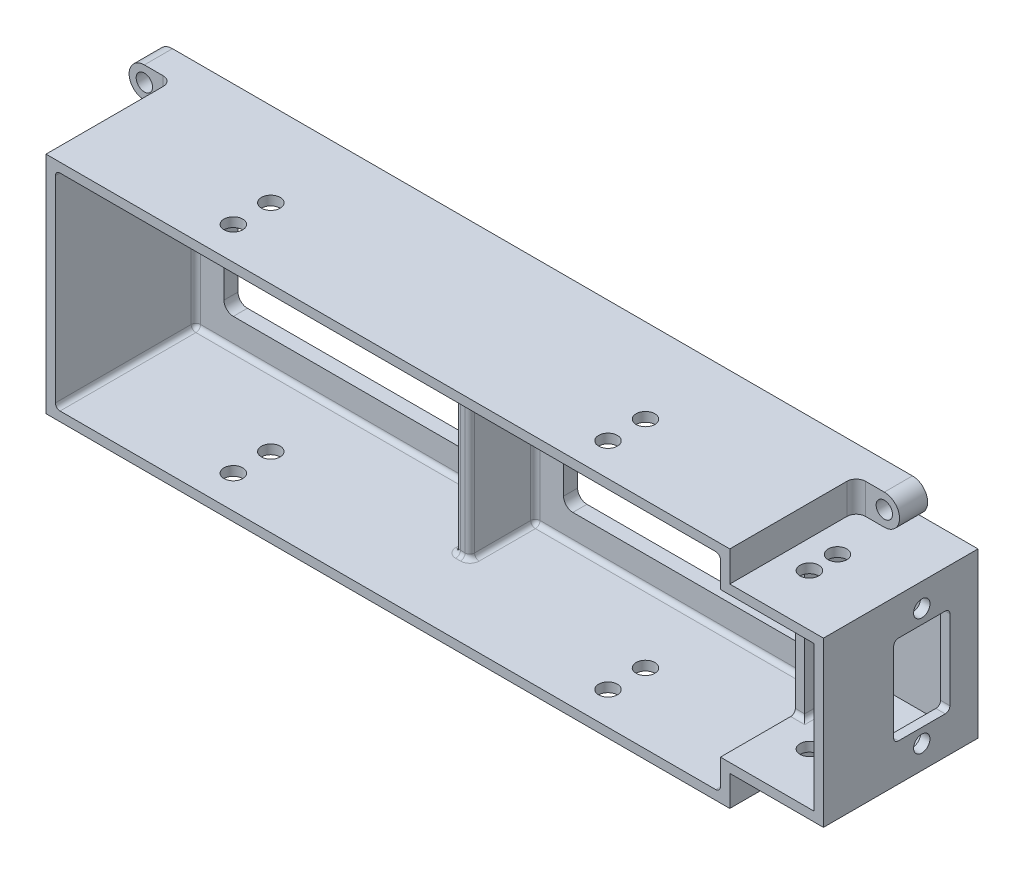
SolidWorks part; units mm, degrees
ref_plane "Top Plane" through (0, 0, 0) normal (0, 0, 1) x (1, 0, 0)
ref_plane "Right Plane" through (0, 0, 0) normal (0, 1, 0) x (1, 0, 0)
ref_plane "Front Plane" through (0, 0, 0) normal (1, 0, 0) x (0, 0, -1)
sketch "Sketch1" plane through (0, 0, 0) normal (0, 0, 1) x (1, 0, 0)
  line L0 (-70, 21) -> (70, -21) construction
  line L1 (-70, 21) -> (70, 21) construction
  line L2 (-70, 21) -> (-70, -21) construction
  line L3 (-70, -21) -> (70, -21) construction
  line L4 (70, 21) -> (70, -21) construction
  line L5 (-71, 22) -> (71, 22) construction
  line L6 (71, 22) -> (71, -22) construction
  line L7 (-71, -22) -> (71, -22) construction
  line L8 (-71, 22) -> (-71, -22) construction
  line L9 (-73, 24) -> (73, 24)
  line L10 (73, 24) -> (73, 17.5)
  line L11 (-73, -24) -> (73, -24)
  line L12 (-73, 24) -> (-73, -24)
  line L13 (73, 17.5) -> (93, 17.5)
  line L14 (93, 17.5) -> (93, -17.5)
  line L15 (-78.4215, 0) -> (137.9248, 0) construction
  line L16 (73, -17.5) -> (93, -17.5)
  line L17 (73, -17.5) -> (73, -24)
  line L18 (73, 24) -> (73, -24) construction
  point P18 (0, 0)
  point P20 (93, 0)
  dimension "D1" = 140
  dimension "D2" = 42
  dimension "D5" = 35
  dimension "D6" = 20
  dimension "D3" = 1
  dimension "D4" = 2
extrude "Boss-Extrude1" add sketch "Sketch1" along normal mid plane 3
sketch "Sketch2" plane through (0, 0, 1.5) normal (0, 0, 1) x (1, 0, 0)
  line L0 (-71, 22) -> (71, 22) construction
  line L1 (71, 22) -> (71, -22) construction
  line L2 (-71, -22) -> (71, -22) construction
  line L3 (-71, 22) -> (-71, -22) construction
  line L4 (-71, 22) -> (71, 22)
  line L5 (71, 22) -> (71, 15.5)
  line L6 (-71, -22) -> (71, -22)
  line L7 (-71, 22) -> (-71, -22)
  line L8 (71, -15.5) -> (91, -15.5)
  line L9 (91, -15.5) -> (91, 15.5)
  line L10 (91, 15.5) -> (71, 15.5)
  line L11 (91, 15.5) -> (73, 15.5) construction
  line L12 (-73, 24) -> (-73, -24)
  line L13 (-73, -24) -> (73, -24)
  line L14 (73, 17.5) -> (73, 24)
  line L15 (73, 24) -> (-73, 24)
  line L16 (-73, 24) -> (-73, -24)
  line L17 (-73, -24) -> (73, -24)
  line L18 (73, 17.5) -> (73, 24)
  line L19 (73, 24) -> (-73, 24)
  line L20 (73, -15.5) -> (91, -15.5) construction
  line L21 (71, -15.5) -> (71, -22)
  line L24 (73, -24) -> (73, -17.5)
  line L25 (73, -24) -> (73, -17.5)
  line L26 (73, -17.5) -> (93, -17.5)
  line L27 (73, -17.5) -> (93, -17.5)
  line L28 (93, -17.5) -> (93, 17.5)
  line L29 (93, -17.5) -> (93, 17.5)
  line L30 (93, 17.5) -> (73, 17.5)
  line L31 (93, 17.5) -> (73, 17.5)
  point P11 (71, 15.5)
  point P14 (71, -15.5)
  point P18 (71, 15.5)
  dimension "D1" = 0
  dimension "D2" = 2
extrude "Boss-Extrude2" add sketch "Sketch2" along normal blind 30
sketch "Sketch3" plane through (0, 0, 1.5) normal (0, 0, 1) x (1, 0, 0)
  line L0 (91, 15.5) -> (71, 15.5) construction
  line L1 (-1.5, 22) -> (1.5, 22)
  line L2 (-1.5, 22) -> (-1.5, -22)
  line L3 (-1.5, -22) -> (1.5, -22)
  line L4 (1.5, 22) -> (1.5, -22)
  line L5 (71, -15.5) -> (73, -15.5)
  line L6 (-1.5, 22) -> (1.5, -22) construction
  line L7 (71, -15.5) -> (71, 15.5)
  line L8 (71, 15.5) -> (73, 15.5)
  line L9 (-71, -22) -> (71, -22) construction
  line L10 (73, -15.5) -> (73, 15.5)
  dimension "D1" = 3
  dimension "D2" = 2
extrude "Boss-Extrude3" add sketch "Sketch3" along normal blind 14
sketch "Sketch5" plane through (0, 0, 1.5) normal (0, 0, 1) x (1, 0, 0)
  line L4 (0, -30.015) -> (0, 35.8775) construction
  line L5 (65, 16) -> (65, -16)
  line L6 (7.5, 16) -> (65, 16)
  line L7 (7.5, -16) -> (7.5, 16)
  line L8 (-65, -16) -> (-7.5, -16)
  line L9 (-7.5, -16) -> (-7.5, 16)
  line L10 (-7.5, 16) -> (-65, 16)
  line L11 (-65, 16) -> (-65, -16)
  line L12 (-65, -16) -> (-7.5, -16)
  line L13 (-7.5, -16) -> (-7.5, 16)
  line L14 (-7.5, 16) -> (-65, 16)
  line L15 (-65, 16) -> (-65, -16)
  line L16 (65, -16) -> (7.5, -16)
  dimension "D1" = 6
extrude "Cut-Extrude1" cut sketch "Sketch5" against normal through all
sketch "Sketch6" plane through (0, 0, -1.5) normal (0, 0, -1) x (-1, 0, 0)
  line L0 (-79, 24) -> (-73, 24)
  line L1 (-93, 17.5) -> (-73, 17.5) construction
  line L2 (-73, 17.5) -> (-73, 24) construction
  line L3 (-79, 17.5) -> (-73, 17.5)
  line L4 (-73, 17.5) -> (-73, 24)
  line L5 (-108.1843, 0) -> (78.2725, 0) construction
  line L6 (-73, -17.5) -> (-73, -24)
  line L7 (-79, -17.5) -> (-73, -17.5)
  line L8 (-79, -24) -> (-73, -24)
  line L9 (0, 28.6257) -> (0, -28.9986) construction
  line L10 (79, -24) -> (73, -24)
  line L11 (79, -17.5) -> (73, -17.5)
  line L12 (73, -17.5) -> (73, -24)
  line L13 (73, 17.5) -> (73, 24)
  line L14 (79, 17.5) -> (73, 17.5)
  line L15 (79, 24) -> (73, 24)
  arc A0 (-79, 24) -> (-79, 17.5) centre (-79, 20.75) ccw
  arc A1 (-79, -24) -> (-79, -17.5) centre (-79, -20.75) cw
  arc A2 (79, -24) -> (79, -17.5) centre (79, -20.75) ccw
  arc A3 (79, 24) -> (79, 17.5) centre (79, 20.75) cw
  circle A4 centre (-79, 20.75) radius 3 construction
  circle A5 centre (-79, 20.75) radius 1.75 construction
  circle A6 centre (-79, -20.75) radius 1.75 construction
  circle A7 centre (-79, -20.75) radius 3 construction
  circle A8 centre (79, -20.75) radius 3 construction
  circle A9 centre (79, -20.75) radius 1.75 construction
  circle A10 centre (79, 20.75) radius 1.75 construction
  circle A11 centre (79, 20.75) radius 3 construction
  dimension "D1" = 6.5
  dimension "D3" = 6
  dimension "D4" = 3.5
  dimension "D2" = 6
extrude "Boss-Extrude4" add sketch "Sketch6" against normal blind 6
sketch "Sketch7" plane through (0, 0, -1.5) normal (0, 0, -1) x (-1, 0, 0)
  circle A0 centre (79, -20.75) radius 1.75 construction
  circle A1 centre (79, 20.75) radius 1.75 construction
  circle A2 centre (-79, -20.75) radius 1.75 construction
  circle A3 centre (-79, 20.75) radius 1.75 construction
  circle A4 centre (79, -20.75) radius 1.75
  circle A5 centre (79, 20.75) radius 1.75
  circle A6 centre (-79, -20.75) radius 1.75
  circle A7 centre (-79, 20.75) radius 1.75
extrude "Cut-Extrude2" cut sketch "Sketch7" against normal through all
sketch "Sketch8" plane through (93, 0, 0) normal (1, 0, 0) x (0, 0, -1)
  line L0 (-16.9, 16) -> (-4.1, -16) construction
  line L1 (-16.9, 16) -> (-4.1, 16) construction
  line L2 (-16.9, 16) -> (-16.9, -16) construction
  line L3 (-16.9, -16) -> (-4.1, -16) construction
  line L4 (-4.1, 16) -> (-4.1, -16) construction
  line L5 (-16.9, 0) -> (-4.1, 0) construction
  line L8 (-16.5, 9.5) -> (-4.5, -9.5) construction
  line L9 (-16.5, 9.5) -> (-4.5, 9.5)
  line L10 (-16.5, 9.5) -> (-16.5, -9.5)
  line L11 (-16.5, -9.5) -> (-4.5, -9.5)
  line L12 (-4.5, 9.5) -> (-4.5, -9.5)
  line L15 (1.5, -17.5) -> (1.5, 17.5) construction
  circle A0 centre (-10.5, 12.5) radius 1.75
  circle A1 centre (-10.5, -12.5) radius 1.75
  point P6 (0, 0)
  point P7 (-22.9, 0)
  point P10 (-7.648, 0)
  point P12 (-10.5, 0)
  point P20 (0, 0)
  point P21 (0, 0)
  point P22 (-16.5, 0)
  point P23 (0, 0)
  point P24 (0, 0)
  dimension "D2" = 3.5
  dimension "D1" = 32
  dimension "D3" = 25
  dimension "D4" = 12.8
  dimension "D5" = 19
  dimension "D6" = 12
  dimension "D7" = 12
extrude "Cut-Extrude3" cut sketch "Sketch8" against normal up to next
fillet "Fillet5" radius 1 4 edges at (92, 9.5, 4.5) (92, 9.5, 16.5) (92, -9.5, 16.5) (92, -9.5, 4.5)
sketch "Sketch9" plane through (0, 0, 0) normal (0, 1, 0) x (1, 0, 0)
  line L0 (0, 13.3661) -> (0, -52.7564) construction
  line L1 (79, 1.5) -> (-79, 1.5) construction
  circle A0 centre (-40, -24.5) radius 2
  circle A1 centre (-40, -16.5) radius 2
  circle A2 centre (40, -16.5) radius 2
  circle A3 centre (40, -24.5) radius 2
  dimension "D1" = 8
  dimension "D2" = 4
  dimension "D3" = 18
  dimension "D4" = 80
extrude "Cut-Extrude4" cut sketch "Sketch9" against normal through all both and the other way through all
fillet "Fillet1" radius 1 2 edges at (1.5, 0, 15.5) (-1.5, 0, 15.5)
fillet "Fillet2" radius 2 8 edges at (65, 16, 0) (65, -16, 0) (7.5, 16, 0) (7.5, -16, 0) (-7.5, -16, 0) (-7.5, 16, 0) (-65, 16, 0) (-65, -16, 0)
fillet "Fillet3" radius 2 4 edges at (73, 20.75, 4.5) (73, -20.75, 4.5) (-73, 20.75, 4.5) (-73, -20.75, 4.5)
fillet "Fillet4" radius 5 2 edges at (-73, -17.5, 2.5) (-73, 17.5, 2.5)
fillet "Fillet6" radius 1 2 edges at (72, 15.5, 15.5) (72, -15.5, 15.5)
fillet "Fillet7" radius 1 8 edges at (-71, 0, 1.5) (-36.25, 22, 1.5) (-1.5, 0, 1.5) (-36.25, -22, 1.5) (1.5, 0, 1.5) (36.25, 22, 1.5) (71, 0, 1.5) (36.25, -22, 1.5)
fillet "Fillet8" radius 1 24 edges at (-1.7929, 21.7071, 1.7929) (-1.5, 22, 8.5) (-1.2071, 22, 15.2071) (0, 22, 15.5) (1.2071, 22, 15.2071) (1.7929, 21.7071, 1.7929) (-1.7929, -21.7071, 1.7929) (-1.5, -22, 8.5) (-1.2071, -22, 15.2071) (0, -22, 15.5) (1.2071, -22, 15.2071) (1.7929, -21.7071, 1.7929) (-70.7071, -21.7071, 1.7929) (-70.7071, 21.7071, 1.7929) (70.7071, 21.7071, 1.7929) (70.7071, -21.7071, 1.7929) (1.5, 22, 8.5) (1.5, -22, 8.5) (73, 15.5, 9) (73, -15.5, 9) (-71, -22, 17) (-71, 22, 17) (71, 22, 17) (71, -22, 17)
sketch "Sketch10" plane through (0, 17.5, 0) normal (0, 1, 0) x (1, 0, 0)
  line L0 (93, 1.5) -> (79, 1.5) construction
  line L1 (93, -31.5) -> (93, 1.5) construction
  circle A0 centre (79, -14.5) radius 2
  circle A1 centre (79, -20.5) radius 2
  point P4 (0, 0)
  point P7 (81.2615, -14.5)
  dimension "D1" = 4
  dimension "D2" = 6
  dimension "D3" = 16
  dimension "D4" = 14
extrude "Cut-Extrude5" cut sketch "Sketch10" against normal through all
